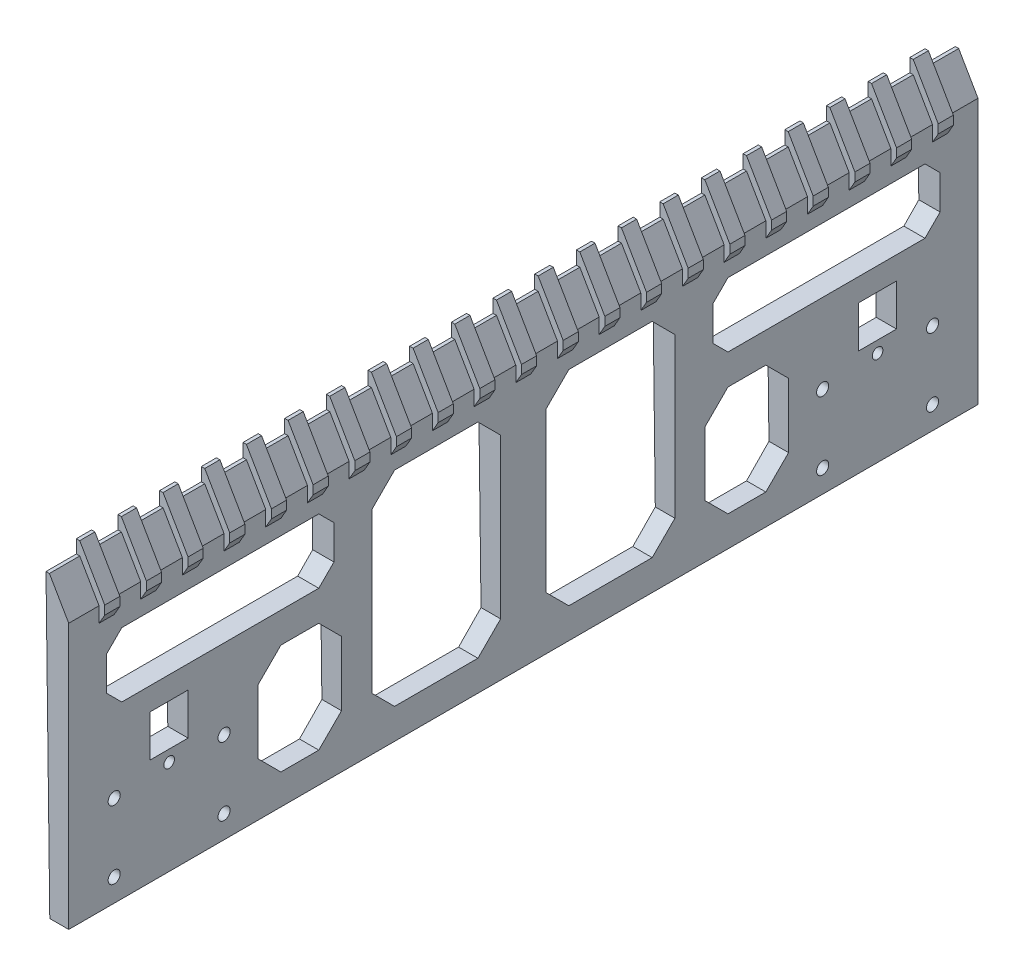
SolidWorks part; units mm, degrees
ref_plane "前视基准面" through (0, 0, 0) normal (0, 0, 1) x (1, 0, 0)
ref_plane "上视基准面" through (0, 0, 0) normal (0, 1, 0) x (1, 0, 0)
ref_plane "右视基准面" through (0, 0, 0) normal (1, 0, 0) x (0, 0, -1)
sketch "草图1" plane through (0, 0, 0) normal (1, 0, 0) x (0, 0, -1)
  line L1 (0, 0) -> (240, 0)
  line L2 (0, 0) -> (0, -70)
  line L3 (0, -70) -> (240, -70)
  line L4 (240, 0) -> (240, -70)
  dimension "D1" = 240
  dimension "D2" = 70
extrude "凸台-拉伸1" add sketch "草图1" along normal blind 6
sketch "草图3" plane through (6, 0, 0) normal (1, 0, 0) x (0, 0, -1)
  line L0 (120, 0) -> (120, -70) construction
  line L1 (14, -8) -> (66, -8)
  line L2 (10, -12) -> (10, -21)
  line L3 (14, -25) -> (66, -25)
  line L4 (70, -12) -> (70, -21)
  line L5 (240, 0) -> (0, 0) construction
  line L6 (0, -70) -> (240, -70) construction
  line L7 (0, 0) -> (0, -70) construction
  line L12 (10, -12) -> (14, -8)
  line L13 (10, -21) -> (14, -25)
  line L14 (66, -25) -> (70, -21)
  line L15 (66, -8) -> (70, -12)
  line L28 (80, -14) -> (86, -8)
  line L36 (50, -56) -> (56, -62)
  line L42 (86, -8) -> (108, -8)
  line L43 (80, -14) -> (80, -56)
  line L44 (86, -62) -> (108, -62)
  line L45 (114, -14) -> (114, -56)
  line L46 (108, -8) -> (114, -14)
  line L47 (108, -62) -> (114, -56)
  line L48 (80, -56) -> (86, -62)
  line L49 (56, -33) -> (66, -33)
  line L50 (50, -39) -> (50, -56)
  line L51 (56, -62) -> (66, -62)
  line L52 (72, -39) -> (72, -56)
  line L53 (66, -62) -> (72, -56)
  line L54 (66, -33) -> (72, -39)
  line L55 (50, -39) -> (56, -33)
  point P0 (10, -8)
  point P1 (70, -25)
  point P2 (10, -25)
  point P3 (70, -8)
  point P20 (80, -8)
  point P21 (114, -62)
  point P22 (80, -62)
  point P23 (114, -8)
  point P24 (50, -33)
  point P33 (72, -62)
  point P34 (50, -62)
  point P35 (72, -33)
  dimension "D1" = 10
  dimension "D2" = 8
  dimension "D3" = 17
  dimension "D4" = 60
  dimension "D5" = 8
  dimension "D6" = 8
  dimension "D7" = 54
  dimension "D12" = 80
  dimension "D13" = 6
  dimension "D14" = 34
  dimension "D15" = 10
  dimension "D16" = 8
  dimension "D21" = 8
  dimension "D22" = 29
  dimension "D23" = 22
extrude "切除-拉伸2" cut sketch "草图3" against normal through all
sketch "草图2" plane through (0, 0, 0) normal (1, 0, 0) x (0, 0, -1)
  line L0 (0, 0) -> (0, -70) construction
  line L1 (12, -46) -> (41, -46) construction
  line L2 (12, -46) -> (12, -64) construction
  line L3 (12, -64) -> (41, -64) construction
  line L4 (41, -46) -> (41, -64) construction
  line L5 (240, 0) -> (0, 0) construction
  line L6 (120, 0) -> (120, -70) construction
  circle A0 centre (12, -46) radius 1.55
  circle A1 centre (41, -64) radius 1.55
  circle A2 centre (41, -46) radius 1.55
  circle A3 centre (12, -64) radius 1.55
  dimension "D5" = 3.1
  dimension "D1" = 12
  dimension "D2" = 46
  dimension "D3" = 29
  dimension "D4" = 18
sketch "草图6" plane through (0, 0, 0) normal (0, 0, 1) x (1, 0, 0)
  line L0 (6, 0) -> (0, 0)
  line L1 (0, 0) -> (0, 8.8335)
  line L2 (0.9, 8.8335) -> (6, 0)
  line L3 (0, 8.8335) -> (0.9, 8.8335)
  line L4 (0, 8.8335) -> (0, 10.3923) construction
  line L5 (0, 10.3923) -> (0.9, 8.8335) construction
  dimension "D1" = 30
  dimension "D2" = 0.9
extrude "凸台-拉伸2" add sketch "草图6" against normal blind 240
ref_plane "基准面1" through (0, 0, -120) normal (0, 0, 1) x (1, 0, 0)
sketch "草图8" plane through (0, 0, -120) normal (0, 0, 1) x (1, 0, 0)
  line L0 (0, 10.3923) -> (0, 12.3335)
  line L1 (0.9, 12.3335) -> (7.5, 0.9019)
  line L2 (7.5, 0.9019) -> (7.5, -1.4019)
  line L3 (7.5, -4) -> (6, -4) construction
  line L4 (6, 0) -> (6, -70) construction
  line L5 (6, -4) -> (6, 0)
  line L6 (6, 0) -> (0.9, 8.8335) construction
  line L7 (6, 0) -> (0.9, 8.8335)
  line L8 (0, 12.3335) -> (0.9, 12.3335)
  line L9 (0, 12.3335) -> (0, 13.8923) construction
  line L10 (0, 13.8923) -> (0.9, 12.3335) construction
  line L11 (0, 10.3923) -> (0, 8.8335)
  line L12 (0, 8.8335) -> (0.9, 8.8335)
  line L13 (0.9, 8.8335) -> (0, 10.3923) construction
  line L14 (6, -4) -> (7.5, -1.4019)
  line L15 (7.5, -1.4019) -> (7.5, -4) construction
  dimension "D1" = 3.5
  dimension "D2" = 1.5
  dimension "D3" = 4
  dimension "D4" = 0.9
  dimension "D5" = 30
extrude "凸台-拉伸3" add sketch "草图8" along normal mid plane 4
pattern_linear "阵列(线性)1" count 11 spacing 11 along (0, 0, 1) count 11 spacing 11 along (0, 0, -1) of "凸台-拉伸3"
hole_wizard "打孔尺寸(%根据)内六角圆柱头螺钉的类型1" positions "草图14" profile "草图15" counterbore size "M3" standard "GB" end condition through all
sketch "草图14" plane through (0, 0, 0) normal (-1, 0, 0) x (0, 0, 1)
  point P0 (-41, -46)
  point P3 (-12, -46)
  point P6 (-12, -64)
  point P9 (-41, -64)
sketch "草图15" plane through (0, -46, -41) normal (0, 1, 0) x (0, 0, 1)
  line L0 (0, 0) -> (0, 7.5)
  line L1 (0, 7.5) -> (1.6, 7.5)
  line L3 (1.6, 7.5) -> (1.6, 3.4)
  line L4 (1.6, 3.4) -> (3, 3.4)
  line L5 (3, 3.4) -> (3, 0)
  line L7 (3, 0) -> (0, 0)
  line L11 (0, -6.35) -> (0, 107.95) construction
  dimension "通孔孔直径" = 3.2
  dimension "通孔孔深度" = 7.5
  dimension "柱形沉头孔直径" = 6
  dimension "柱形沉头孔深度" = 3.4
sketch "草图16" plane through (0, 0, 0) normal (-1, 0, 0) x (0, 0, 1)
  line L0 (-12, -46) -> (-41, -46) construction
  line L1 (-26.5, -46) -> (-26.5, -25) construction
  line L2 (-14, -25) -> (-66, -25) construction
  line L3 (-26.5, -46) -> (-26.5, -70) construction
  line L4 (0, -70) -> (-240, -70) construction
  circle A0 centre (-26.5, -45.0233) radius 1.4
  dimension "D1" = 2.8
extrude "切除-拉伸3" cut sketch "草图16" against normal blind 10
mirror "镜向1" about plane through (0, 0, -120) normal (0, 0, 1) of "打孔尺寸(%根据)内六角圆柱头螺钉的类型1"
mirror "镜向2" about plane through (0, 0, -120) normal (0, 0, 1) of "切除-拉伸3", "切除-拉伸2"
sketch "草图17" plane through (0, 0, 0) normal (-1, 0, 0) x (0, 0, 1)
  line L0 (0, 8.8335) -> (0, -70) construction
  line L1 (-31.5, -31) -> (-21.5, -31)
  line L2 (-31.5, -31) -> (-31.5, -42)
  line L3 (-31.5, -42) -> (-21.5, -42)
  line L4 (-21.5, -31) -> (-21.5, -42)
  line L6 (0, -70) -> (-240, -70) construction
  line L7 (-120, -70) -> (-120, -8.018) construction
  line L8 (-208.5, -31) -> (-218.5, -31)
  line L9 (-208.5, -31) -> (-208.5, -42)
  line L10 (-208.5, -42) -> (-218.5, -42)
  line L11 (-218.5, -31) -> (-218.5, -42)
  dimension "D1" = 10
  dimension "D2" = 11
  dimension "D3" = 21.5
  dimension "D4" = 28
extrude "切除-拉伸4" cut sketch "草图17" against normal through all
sketch "草图18" plane through (0, 0, 0) normal (0, 0, 1) x (1, 0, 0)
  line L0 (0, -70) -> (1, -70)
  line L1 (6, -70) -> (0, -70) construction
  line L4 (1, -70) -> (0, 8.8335)
  line L5 (0, 8.8335) -> (0, -70)
  dimension "D1" = 1
extrude "切除-拉伸5" cut sketch "草图18" against normal up to next
